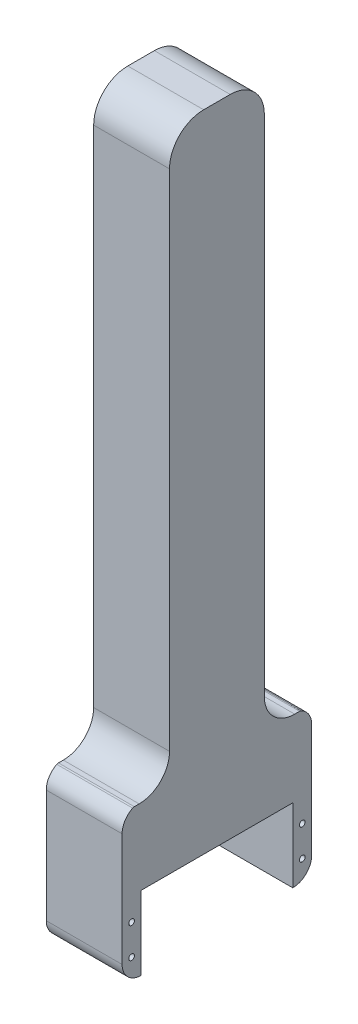
SolidWorks part; units mm, degrees
ref_plane "Front Plane" through (0, 0, 0) normal (0, 0, 1) x (1, 0, 0)
ref_plane "Top Plane" through (0, 0, 0) normal (0, 1, 0) x (1, 0, 0)
ref_plane "Right Plane" through (0, 0, 0) normal (1, 0, 0) x (0, 0, -1)
sketch "Sketch1" plane through (0, 0, 0) normal (1, 0, 0) x (0, 0, -1)
  line L0 (-26.5891, -87.0078) -> (-26.5891, 194.1419) construction
  line L1 (-39.0891, -15.9535) -> (-39.0891, 117.0465)
  line L2 (-56.5891, -31.9535) -> (-56.5891, -55.9535)
  line L3 (-48.5891, -63.9535) -> (-46.5891, -63.9535)
  line L4 (-46.5891, -63.9535) -> (-46.5891, -43.9535)
  line L5 (-46.5891, -43.9535) -> (-6.5891, -43.9535)
  line L6 (-6.5891, -43.9535) -> (-6.5891, -63.9535)
  line L7 (-6.5891, -63.9535) -> (-4.5891, -63.9535)
  line L8 (3.4109, -55.9535) -> (3.4109, -31.9535)
  line L9 (-48.5891, -23.9535) -> (-47.0891, -23.9535)
  line L10 (-4.5891, -23.9535) -> (-6.0891, -23.9535)
  line L11 (-14.0891, -15.9535) -> (-14.0891, 117.0465)
  line L12 (-30.0891, 126.0465) -> (-23.0891, 126.0465)
  arc A0 (-14.0891, -15.9535) -> (-6.0891, -23.9535) centre (-6.0891, -15.9535) ccw
  arc A1 (3.4109, -31.9535) -> (-4.5891, -23.9535) centre (-4.5891, -31.9535) ccw
  arc A2 (-48.5891, -23.9535) -> (-56.5891, -31.9535) centre (-48.5891, -31.9535) ccw
  arc A3 (-47.0891, -23.9535) -> (-39.0891, -15.9535) centre (-47.0891, -15.9535) ccw
  arc A4 (-48.5891, -63.9535) -> (-56.5891, -55.9535) centre (-48.5891, -55.9535) cw
  arc A5 (3.4109, -55.9535) -> (-4.5891, -63.9535) centre (-4.5891, -55.9535) cw
  arc A6 (-14.0891, 117.0465) -> (-23.0891, 126.0465) centre (-23.0891, 117.0465) ccw
  arc A7 (-30.0891, 126.0465) -> (-39.0891, 117.0465) centre (-30.0891, 117.0465) ccw
  point P15 (-26.5891, -43.9535)
  point P18 (-14.0891, -23.9535)
  point P22 (-56.5891, -23.9535)
  point P25 (-39.0891, -23.9535)
  point P28 (-56.5891, -63.9535)
  point P31 (3.4109, -63.9535)
  point P34 (-14.0891, 126.0465)
  point P37 (-39.0891, 126.0465)
  dimension "D9" = 8
  dimension "D2" = 8
  dimension "D10" = 8
  dimension "D11" = 8
  dimension "D12" = 8
  dimension "D13" = 9
  dimension "D1" = 150
  dimension "D3" = 20
  dimension "D4" = 12.5
  dimension "D5" = 40
  dimension "D6" = 10
  dimension "D7" = 10
  dimension "D8" = 40
extrude "Boss-Extrude1" add sketch "Sketch1" along normal blind 20
sketch "Sketch2" plane through (0, 0, 0) normal (-1, 0, 0) x (0, 0, 1)
  line L0 (4.0891, -47.2133) -> (4.0891, -59.7345) construction
  line L1 (49.0891, -44.0987) -> (49.0891, -60.4197) construction
  line L2 (6.5891, -43.9535) -> (6.5891, -63.9535) construction
  line L3 (46.5891, -63.9535) -> (46.5891, -43.9535) construction
  circle A0 centre (4.0891, -49.9535) radius 0.75
  circle A1 centre (4.0891, -57.9535) radius 0.75
  circle A2 centre (49.0891, -57.9535) radius 0.75
  circle A3 centre (49.0891, -49.9535) radius 0.75
  dimension "D3" = 1.5
  dimension "D4" = 1.5
  dimension "D5" = 1.5
  dimension "D6" = 1.5
  dimension "D1" = 2.5
  dimension "D2" = 2.5
extrude "Cut-Extrude1" cut sketch "Sketch2" against normal through all
sketch "Sketch3" plane through (0, 0, 0) normal (-1, 0, 0) x (0, 0, 1)
  line L0 (1.5891, -43.9535) -> (-3.4109, -43.9535)
  line L1 (-3.4109, -55.9535) -> (-3.4109, -31.9535) construction
  line L2 (1.5891, -43.9535) -> (1.5891, -58.3697)
  line L3 (6.5891, -63.3697) -> (6.5891, -71.2983)
  line L4 (26.5891, -43.9535) -> (26.5891, -30.4373) construction
  line L5 (46.5891, -43.9535) -> (6.5891, -43.9535) construction
  line L6 (26.5891, -30.4373) -> (26.5891, -80.0084) construction
  line L7 (46.5891, -63.3697) -> (46.5891, -71.2983)
  line L8 (51.5891, -43.9535) -> (51.5891, -58.3697)
  line L9 (51.5891, -43.9535) -> (56.5891, -43.9535)
  line L10 (-3.4109, -43.9535) -> (-12.9956, -43.9535)
  line L11 (-12.9956, -43.9535) -> (-12.9956, -71.2983)
  line L12 (-12.9956, -71.2983) -> (6.5891, -71.2983)
  line L13 (56.5891, -43.9535) -> (65.1857, -43.9535)
  line L14 (65.1857, -43.9535) -> (65.1857, -71.2983)
  line L15 (65.1857, -71.2983) -> (46.5891, -71.2983)
  arc A0 (-3.4109, -55.9535) -> (4.5891, -63.9535) centre (4.5891, -55.9535) ccw construction
  arc A1 (1.5891, -58.3697) -> (6.5891, -63.3697) centre (6.5891, -58.3697) ccw
  arc A2 (51.5891, -58.3697) -> (46.5891, -63.3697) centre (46.5891, -58.3697) cw
  point P12 (1.5891, -63.3697)
  dimension "D1" = 5
extrude "Cut-Extrude2" cut sketch "Sketch3" against normal through all
fillet "Fillet1" radius 5 1 edges at (10, -43.9535, -3.4109)
fillet "Fillet2" radius 1 1 edges at (10, -43.9535, 1.5891)
fillet "Fillet3" radius 5 1 edges at (10, -43.9535, 56.5891)
fillet "Fillet4" radius 1 1 edges at (10, -43.9535, 51.5891)
sketch "Sketch4" plane through (0, 0, 0) normal (-1, 0, 0) x (0, 0, 1)
  line L0 (1.5891, -47.2949) -> (1.5891, -24.5373)
  line L1 (1.5891, -58.3697) -> (1.5891, -44.8696) construction
  line L2 (1.5891, -24.5373) -> (-18.2928, -24.5373)
  line L3 (-18.2928, -24.5373) -> (-18.2928, -47.2949)
  line L4 (-18.2928, -47.2949) -> (1.5891, -47.2949)
  line L5 (51.5891, -47.2949) -> (51.5891, -22.3191)
  line L6 (51.5891, -44.8696) -> (51.5891, -58.3697) construction
  line L7 (51.5891, -22.3191) -> (73.9945, -22.3191)
  line L8 (73.9945, -22.3191) -> (73.9945, -45.9738)
  line L9 (73.9945, -45.9738) -> (51.5891, -47.2949)
  arc A0 (4.5891, -23.9535) -> (-3.4109, -31.9535) centre (4.5891, -31.9535) ccw construction
extrude "Cut-Extrude3" cut sketch "Sketch4" against normal through all
fillet "Fillet5" radius 5 1 edges at (10, -24.5373, 1.5891)
fillet "Fillet6" radius 1 1 edges at (10, -23.9535, 4.5891)
fillet "Fillet7" radius 5 1 edges at (10, -24.5373, 51.5891)
fillet "Fillet8" radius 1 1 edges at (10, -23.9535, 48.5891)
